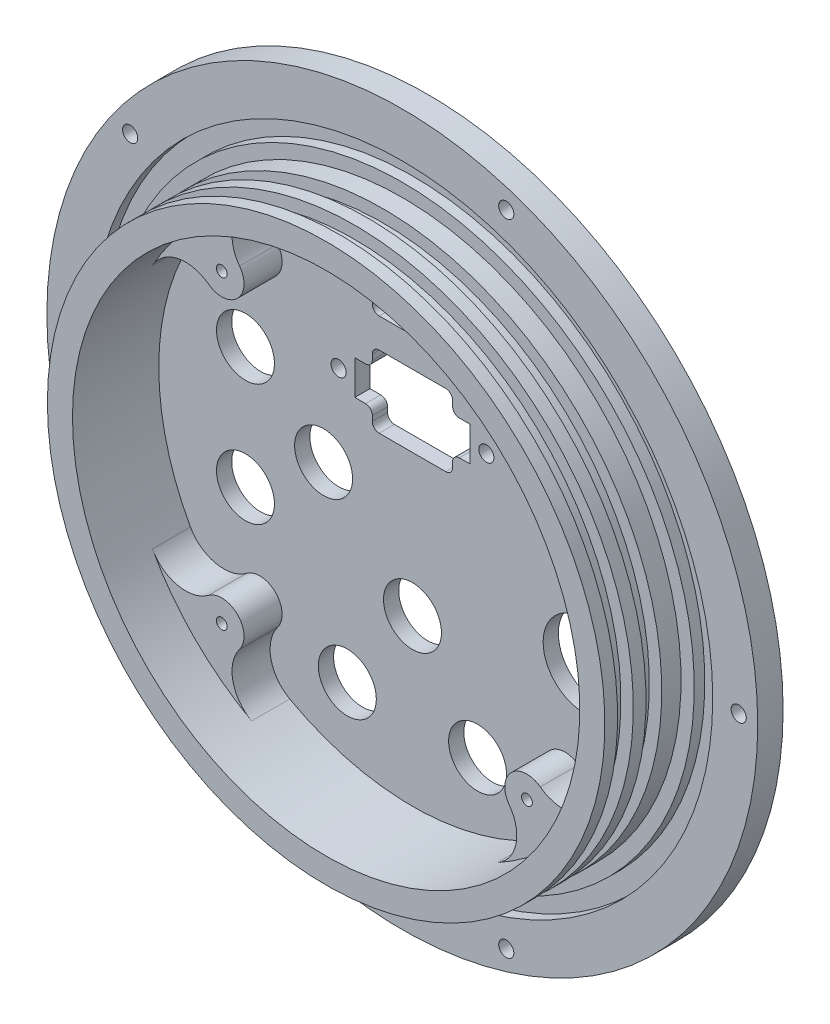
SolidWorks part; units mm, degrees
material "6061-T6 (SS)"
ref_plane "Front Plane" through (0, 0, 0) normal (0, 0, 1) x (1, 0, 0)
ref_plane "Top Plane" through (0, 0, 0) normal (0, 1, 0) x (1, 0, 0)
ref_plane "Right Plane" through (0, 0, 0) normal (1, 0, 0) x (0, 0, -1)
sketch "Sketch1" plane through (0, 0, 0) normal (0, 1, 0) x (1, 0, 0)
  line L0 (0, 0) -> (0, -25.4) construction
  line L1 (0, 0) -> (88.9, 0)
  line L2 (63.4492, -25.4) -> (69.723, -25.4)
  line L3 (69.723, -25.4) -> (69.723, -22.225)
  line L4 (63.4492, -25.4) -> (63.4492, -3.81)
  line L5 (63.4492, -3.81) -> (0, -3.81)
  line L6 (0, -3.81) -> (0, 0)
  line L7 (88.9, 0) -> (88.9, -6.35)
  line L8 (73.025, -3.7084) -> (77.6478, -3.7084)
  line L9 (73.025, -3.7084) -> (73.025, -6.35)
  line L10 (73.025, -6.35) -> (69.723, -6.35)
  line L11 (77.6478, -3.7084) -> (77.6478, -6.35)
  line L12 (77.6478, -6.35) -> (88.9, -6.35)
  line L13 (69.723, -22.225) -> (66.6242, -22.225)
  line L14 (66.6242, -22.225) -> (66.6242, -18.288)
  line L15 (66.6242, -18.288) -> (69.723, -18.288)
  line L16 (69.723, -15.113) -> (66.6242, -15.113)
  line L17 (66.6242, -15.113) -> (66.6242, -11.176)
  line L18 (66.6242, -11.176) -> (69.723, -11.176)
  line L19 (69.723, -11.176) -> (69.723, -6.35)
  line L20 (69.723, -18.288) -> (69.723, -15.113)
  dimension "D1" = 139.446
  dimension "D2" = 6.35
  dimension "D3" = 177.8
  dimension "D4" = 146.05
  dimension "D5" = 3.175
  dimension "D6" = 19.05
  dimension "D7" = 4.6228
  dimension "D8" = 2.6416
  dimension "D9" = 3.0988
  dimension "D10" = 3.937
  dimension "D11" = 3.175
  dimension "D12" = 3.175
  dimension "D13" = 3.81
revolve "Revolve1" add sketch "Sketch1" angle 360 about L0
hole_wizard "#6 Clearance Hole1" positions "Sketch3" profile "Sketch2" hole size "#6" standard "ANSI Inch"
sketch "Sketch3" plane through (0, 0, 6.35) normal (0, 0, 1) x (1, 0, 0)
  line L14 (0, 77.6478) -> (0, 83.2739) construction
  line L17 (0, 83.2739) -> (0, 88.9) construction
  line L19 (0, 0) -> (84.1375, 0) construction
  circle A6 centre (0, 0) radius 84.1375
  circle A7 centre (0, 0) radius 77.6478 construction
  circle A8 centre (0, 0) radius 88.9 construction
  point P192 (84.1375, 0)
  point P208 (25.9999, -80.0195)
  point P209 (-68.0687, -49.4548)
  point P210 (-68.0687, 49.4548)
  point P211 (25.9999, 80.0195)
  dimension "D1" = 5
  dimension "D2" = 168.275
sketch "Sketch2" plane through (84.1375, 0, 6.35) normal (1, 0, 0) x (0, -1, 0)
  line L0 (0, 0) -> (0, 26.5408)
  line L1 (0, 26.5408) -> (1.8986, 25.4)
  line L2 (1.8986, 25.4) -> (1.8986, 0)
  line L5 (1.8986, 0) -> (0, 0)
  line L10 (0, 26.5408) -> (-1.8986, 25.4) construction
  line L11 (0, -6.35) -> (0, 107.95) construction
  dimension "Hole Dia." = 3.7973
  dimension "Hole Depth" = 25.4
  dimension "Drill Angle" = 118
sketch "Sketch4" plane through (0, 0, 3.81) normal (0, 0, 1) x (1, 0, 0)
  line L0 (0, 0) -> (0, 122.2661) construction
  line L1 (-11.7348, 51.9303) -> (-14.4272, 51.9303)
  line L2 (8.3312, 38.6207) -> (-8.3312, 38.6207)
  line L3 (10.033, 40.3225) -> (10.033, 41.6179)
  line L4 (8.3312, 56.6293) -> (-8.3312, 56.6293)
  line L5 (-10.033, 40.3225) -> (-10.033, 41.6179)
  line L6 (10.033, 38.6207) -> (-10.033, 56.6293) construction
  line L7 (10.033, 56.6293) -> (-10.033, 38.6207) construction
  line L8 (-14.4272, 51.9303) -> (-14.4272, 43.3197)
  line L9 (-14.4272, 43.3197) -> (-11.7348, 43.3197)
  line L10 (14.4272, 43.3197) -> (11.7348, 43.3197)
  line L11 (14.4272, 51.9303) -> (14.4272, 43.3197)
  line L12 (11.7348, 51.9303) -> (14.4272, 51.9303)
  line L13 (-14.4272, 47.625) -> (14.4272, 47.625) construction
  line L14 (-10.033, 53.6321) -> (-10.033, 54.9275)
  line L15 (10.033, 53.6321) -> (10.033, 54.9275)
  line L16 (-11.7348, 26.5303) -> (-14.4272, 26.5303)
  line L17 (8.3312, 13.2207) -> (-8.3312, 13.2207)
  line L18 (10.033, 14.9225) -> (10.033, 16.2179)
  line L19 (8.3312, 31.2293) -> (-8.3312, 31.2293)
  line L20 (-10.033, 14.9225) -> (-10.033, 16.2179)
  line L21 (10.033, 13.2207) -> (-10.033, 31.2293) construction
  line L22 (10.033, 31.2293) -> (-10.033, 13.2207) construction
  line L23 (-14.4272, 26.5303) -> (-14.4272, 17.9197)
  line L24 (-14.4272, 17.9197) -> (-11.7348, 17.9197)
  line L25 (14.4272, 26.5303) -> (14.4272, 17.9197)
  line L26 (11.7348, 26.5303) -> (14.4272, 26.5303)
  line L27 (14.4272, 17.9197) -> (11.7348, 17.9197)
  line L28 (-14.4272, 22.225) -> (14.4272, 22.225) construction
  line L29 (-10.033, 28.2321) -> (-10.033, 29.5275)
  line L30 (10.033, 28.2321) -> (10.033, 29.5275)
  line L31 (0, 0) -> (37.8444, 0) construction
  line L32 (-14.4272, -22.225) -> (14.4272, -22.225)
  line L33 (10.033, -31.2293) -> (-10.033, -13.2207)
  line L34 (10.033, -13.2207) -> (-10.033, -31.2293)
  line L35 (-14.4272, -47.625) -> (14.4272, -47.625)
  line L36 (10.033, -56.6293) -> (-10.033, -38.6207)
  line L37 (10.033, -38.6207) -> (-10.033, -56.6293)
  line L38 (10.033, -28.2321) -> (10.033, -29.5275) construction
  line L39 (-10.033, -28.2321) -> (-10.033, -29.5275) construction
  line L40 (14.4272, -17.9197) -> (11.7348, -17.9197) construction
  line L41 (11.7348, -26.5303) -> (14.4272, -26.5303) construction
  line L42 (14.4272, -26.5303) -> (14.4272, -17.9197) construction
  line L43 (-14.4272, -17.9197) -> (-11.7348, -17.9197) construction
  line L44 (-14.4272, -26.5303) -> (-14.4272, -17.9197) construction
  line L45 (-10.033, -14.9225) -> (-10.033, -16.2179) construction
  line L46 (8.3312, -31.2293) -> (-8.3312, -31.2293) construction
  line L47 (10.033, -14.9225) -> (10.033, -16.2179) construction
  line L48 (8.3312, -13.2207) -> (-8.3312, -13.2207) construction
  line L49 (-11.7348, -26.5303) -> (-14.4272, -26.5303) construction
  line L50 (10.033, -53.6321) -> (10.033, -54.9275) construction
  line L51 (-10.033, -53.6321) -> (-10.033, -54.9275) construction
  line L52 (11.7348, -51.9303) -> (14.4272, -51.9303) construction
  line L53 (14.4272, -51.9303) -> (14.4272, -43.3197) construction
  line L54 (14.4272, -43.3197) -> (11.7348, -43.3197) construction
  line L55 (-14.4272, -43.3197) -> (-11.7348, -43.3197) construction
  line L56 (-14.4272, -51.9303) -> (-14.4272, -43.3197) construction
  line L57 (-10.033, -40.3225) -> (-10.033, -41.6179) construction
  line L58 (8.3312, -56.6293) -> (-8.3312, -56.6293) construction
  line L59 (10.033, -40.3225) -> (10.033, -41.6179) construction
  line L60 (8.3312, -38.6207) -> (-8.3312, -38.6207) construction
  line L61 (-11.7348, -51.9303) -> (-14.4272, -51.9303) construction
  line L62 (-14.4272, 22.225) -> (14.4272, 22.225) construction
  arc A0 (-11.7348, 43.3197) -> (-10.033, 41.6179) centre (-11.7348, 41.6179) cw
  arc A1 (11.7348, 43.3197) -> (10.033, 41.6179) centre (11.7348, 41.6179) ccw
  arc A2 (11.7348, 51.9303) -> (10.033, 53.6321) centre (11.7348, 53.6321) cw
  arc A3 (-11.7348, 51.9303) -> (-10.033, 53.6321) centre (-11.7348, 53.6321) ccw
  arc A4 (-8.3312, 38.6207) -> (-10.033, 40.3225) centre (-8.3312, 40.3225) cw
  arc A5 (8.3312, 38.6207) -> (10.033, 40.3225) centre (8.3312, 40.3225) ccw
  arc A6 (10.033, 54.9275) -> (8.3312, 56.6293) centre (8.3312, 54.9275) ccw
  arc A7 (-8.3312, 56.6293) -> (-10.033, 54.9275) centre (-8.3312, 54.9275) ccw
  arc A8 (-11.7348, 17.9197) -> (-10.033, 16.2179) centre (-11.7348, 16.2179) cw
  arc A9 (-8.3312, 13.2207) -> (-10.033, 14.9225) centre (-8.3312, 14.9225) cw
  arc A10 (8.3312, 13.2207) -> (10.033, 14.9225) centre (8.3312, 14.9225) ccw
  arc A11 (11.7348, 17.9197) -> (10.033, 16.2179) centre (11.7348, 16.2179) ccw
  arc A12 (11.7348, 26.5303) -> (10.033, 28.2321) centre (11.7348, 28.2321) cw
  arc A13 (10.033, 29.5275) -> (8.3312, 31.2293) centre (8.3312, 29.5275) ccw
  arc A14 (-8.3312, 31.2293) -> (-10.033, 29.5275) centre (-8.3312, 29.5275) ccw
  arc A15 (-11.7348, 26.5303) -> (-10.033, 28.2321) centre (-11.7348, 28.2321) ccw
  arc A16 (-11.7348, -26.5303) -> (-10.033, -28.2321) centre (-11.7348, -28.2321) cw construction
  arc A17 (-8.3312, -31.2293) -> (-10.033, -29.5275) centre (-8.3312, -29.5275) cw construction
  arc A18 (10.033, -29.5275) -> (8.3312, -31.2293) centre (8.3312, -29.5275) cw construction
  arc A19 (11.7348, -26.5303) -> (10.033, -28.2321) centre (11.7348, -28.2321) ccw construction
  arc A20 (11.7348, -17.9197) -> (10.033, -16.2179) centre (11.7348, -16.2179) cw construction
  arc A21 (8.3312, -13.2207) -> (10.033, -14.9225) centre (8.3312, -14.9225) cw construction
  arc A22 (-8.3312, -13.2207) -> (-10.033, -14.9225) centre (-8.3312, -14.9225) ccw construction
  arc A23 (-11.7348, -17.9197) -> (-10.033, -16.2179) centre (-11.7348, -16.2179) ccw construction
  arc A24 (-8.3312, -56.6293) -> (-10.033, -54.9275) centre (-8.3312, -54.9275) cw construction
  arc A25 (10.033, -54.9275) -> (8.3312, -56.6293) centre (8.3312, -54.9275) cw construction
  arc A26 (8.3312, -38.6207) -> (10.033, -40.3225) centre (8.3312, -40.3225) cw construction
  arc A27 (-8.3312, -38.6207) -> (-10.033, -40.3225) centre (-8.3312, -40.3225) ccw construction
  arc A28 (-11.7348, -51.9303) -> (-10.033, -53.6321) centre (-11.7348, -53.6321) cw construction
  arc A29 (11.7348, -51.9303) -> (10.033, -53.6321) centre (11.7348, -53.6321) ccw construction
  arc A30 (11.7348, -43.3197) -> (10.033, -41.6179) centre (11.7348, -41.6179) cw construction
  arc A31 (-11.7348, -43.3197) -> (-10.033, -41.6179) centre (-11.7348, -41.6179) ccw construction
  point P4 (0, 47.625)
  point P21 (-10.033, 43.3197)
  point P24 (10.033, 43.3197)
  point P27 (10.033, 51.9303)
  point P30 (-10.033, 51.9303)
  point P43 (0, 22.225)
  point P60 (-10.033, 17.9197)
  point P69 (10.033, 17.9197)
  point P72 (10.033, 26.5303)
  point P81 (-10.033, 26.5303)
  point P151 (-10.033, -26.5303)
  point P152 (10.033, -26.5303)
  point P153 (10.033, -17.9197)
  point P154 (-10.033, -17.9197)
  point P155 (0, -22.225)
  point P156 (-10.033, -51.9303)
  point P157 (10.033, -51.9303)
  point P158 (10.033, -43.3197)
  point P159 (-10.033, -43.3197)
  point P160 (0, -47.625)
  dimension "D6" = 1.7018
  dimension "D7" = 1.7018
  dimension "D8" = 1.7018
  dimension "D9" = 1.7018
  dimension "D10" = 1.7018
  dimension "D11" = 1.7018
  dimension "D12" = 1.7018
  dimension "D13" = 1.7018
  dimension "D14" = 1.7018
  dimension "D15" = 1.7018
  dimension "D16" = 1.7018
  dimension "D17" = 1.7018
  dimension "D18" = 1.7018
  dimension "D19" = 1.7018
  dimension "D20" = 1.7018
  dimension "D21" = 1.7018
  dimension "D1" = 20.066
  dimension "D2" = 28.8544
  dimension "D3" = 8.6106
  dimension "D4" = 18.0086
  dimension "D5" = 47.625
  dimension "D22" = 22.225
extrude "Cut-Extrude1" cut sketch "Sketch4" against normal through all contours A15 L16 L23 L24 A8 L20 A9 L17 A10 L18 A11 L27 L25 L26 A12 L30 A13 L19 A14 L29 | L4 A7 L14 A3 L1 L8 L9 A0 L5 A4 L2 A5 L3 A1 L10 L11 L12 A2 L15 A6 region at (0, 47.625, 3.81) region at (0, 22.225, 3.81)
hole_wizard "#6 Clearance Hole2" positions "Sketch6" profile "Sketch5" hole size "#6" standard "ANSI Inch"
sketch "Sketch6" plane through (0, 0, 3.81) normal (0, 0, 1) x (1, 0, 0)
  line L0 (0, 38.6207) -> (0, 56.6293) construction
  line L1 (-8.3312, 38.6207) -> (8.3312, 38.6207) construction
  line L2 (8.3312, 56.6293) -> (-8.3312, 56.6293) construction
  line L5 (-14.4272, 47.625) -> (14.4272, 47.625) construction
  line L6 (-14.4272, 51.9303) -> (-14.4272, 43.3197) construction
  line L7 (14.4272, 43.3197) -> (14.4272, 51.9303) construction
  line L8 (-14.4272, 22.225) -> (14.4272, 22.225) construction
  line L9 (-14.4272, 26.5303) -> (-14.4272, 17.9197) construction
  line L10 (14.4272, 17.9197) -> (14.4272, 26.5303) construction
  point P21 (-18.4785, 47.625)
  point P24 (18.4785, 47.625)
  point P35 (-18.4785, 22.225)
  point P37 (18.4785, 22.225)
  dimension "D1" = 36.957
sketch "Sketch5" plane through (-18.4785, 47.625, 3.81) normal (1, 0, 0) x (0, -1, 0)
  line L0 (0, 0) -> (0, 9.0148)
  line L1 (0, 9.0148) -> (1.8986, 7.874)
  line L2 (1.8986, 7.874) -> (1.8986, 0)
  line L5 (1.8986, 0) -> (0, 0)
  line L10 (0, 9.0148) -> (-1.8987, 7.874) construction
  line L11 (0, -6.35) -> (0, 107.95) construction
  dimension "Hole Dia." = 3.7973
  dimension "Hole Depth" = 7.874
  dimension "Drill Angle" = 118
sketch "Sketch11" plane through (0, 0, 3.81) normal (0, 0, 1) x (1, 0, 0)
  line L0 (-38.1661, 38.1661) -> (38.1661, 38.1661) construction
  line L1 (38.1661, 38.1661) -> (38.1661, -38.1661) construction
  line L2 (38.1661, -38.1661) -> (-38.1661, -38.1661) construction
  line L3 (-38.1661, -38.1661) -> (-38.1661, 38.1661) construction
  line L4 (-41.8875, 34.0402) -> (-48.9307, 40.393)
  line L5 (-34.0402, 41.8875) -> (-40.393, 48.9307)
  line L6 (0, 0) -> (0, 31.159) construction
  line L7 (0, 0) -> (24.8539, 0) construction
  line L8 (41.8875, 34.0402) -> (48.9307, 40.393)
  line L9 (34.0402, 41.8875) -> (40.393, 48.9307)
  line L10 (41.8875, -34.0402) -> (48.9307, -40.393)
  line L11 (34.0402, -41.8875) -> (40.393, -48.9307)
  line L12 (-41.8875, -34.0402) -> (-48.9307, -40.393)
  line L13 (-34.0402, -41.8875) -> (-40.393, -48.9307)
  line L14 (-38.1661, 38.1661) -> (0, 0) construction
  circle A0 centre (0, 0) radius 53.975 construction
  circle A1 centre (-38.1661, 38.1661) radius 5.5562
  circle A2 centre (38.1661, 38.1661) radius 5.5562
  circle A3 centre (38.1661, -38.1661) radius 5.5562
  circle A4 centre (-38.1661, -38.1661) radius 5.5562
  circle A5 centre (0, 0) radius 63.4492 construction
  circle A6 centre (0, 0) radius 63.4492 construction
  arc A7 (-40.393, 48.9307) -> (-48.9307, 40.393) centre (0, 0) ccw
  arc A8 (-48.9307, -40.393) -> (-40.393, -48.9307) centre (0, 0) ccw
  arc A9 (40.393, -48.9307) -> (48.9307, -40.393) centre (0, 0) ccw
  arc A10 (48.9307, 40.393) -> (40.393, 48.9307) centre (0, 0) ccw
  dimension "D1" = 107.95
  dimension "D2" = 11.1125
extrude "Boss-Extrude1" add sketch "Sketch11" along normal blind 9.525 contours L5 A7 L4 A1 | A1 | A2 | L8 A10 L9 A2 | A3 | L11 A9 L10 A3 | L12 A8 L13 A4 | A4 region at (-42.8886, 42.8886, 3.81) region at (-38.1661, 38.1661, 3.81) region at (42.8886, 42.8886, 3.81) region at (38.1661, 38.1661, 3.81) region at (42.8886, -42.8886, 3.81) region at (38.1661, -38.1661, 3.81) region at (-42.8886, -42.8886, 3.81) region at (-38.1661, -38.1661, 3.81)
sketch "Sketch7" plane through (0, 0, 3.81) normal (0, 0, 1) x (1, 0, 0)
  line L0 (52.7617, -8.5918) -> (49.9889, -18.9401)
  line L1 (0, 0) -> (44.45, 0) construction
  line L3 (0, 0) -> (-44.45, 0) construction
  line L4 (0, 0) -> (51.3753, -13.766) construction
  arc A0 (52.7617, -8.5918) -> (49.9889, -18.9401) centre (42.9354, -11.5045) ccw
  circle A2 centre (0, 0) radius 44.45 construction
  dimension "D1" = 20.4978
  dimension "D3" = 88.9
  dimension "D2" = 8.7376
  dimension "D4" = 15
extrude "Cut-Extrude2" cut sketch "Sketch7" against normal through all
fillet "Fillet1" radius 9.525 8 edges at (-48.9307, -40.393, 8.5725) (-40.393, -48.9307, 8.5725) (40.393, -48.9307, 8.5725) (48.9307, -40.393, 8.5725) (48.9307, 40.393, 8.5725) (40.393, 48.9307, 8.5725) (-40.393, 48.9307, 8.5725) (-48.9307, 40.393, 8.5725)
hole_wizard "M16x1.5 Tapped Hole1" positions "Sketch9" profile "Sketch8" tap size "M16x1.5" standard "ANSI Metric"
sketch "Sketch9" plane through (0, 0, 3.81) normal (0, 0, 1) x (1, 0, 0)
  line L7 (0, 0) -> (42.9354, -11.5045) construction
  line L11 (-41.7693, 15.2028) -> (0, 0) construction
  line L13 (0, 0) -> (-59.9493, 0) construction
  line L14 (0, 0) -> (0, -60.9622) construction
  line L15 (0, 0) -> (18.9657, -52.108) construction
  line L16 (0, 0) -> (50.7536, 18.4728) construction
  circle A3 centre (0, 0) radius 44.45
  circle A5 centre (0, 0) radius 47.625
  circle A6 centre (0, 0) radius 22.225
  point P14 (44.7529, 16.2887)
  point P59 (-22.225, 0)
  point P98 (0, -22.225)
  point P112 (-16.2887, -44.7529)
  point P114 (-41.7693, 15.2028)
  point P116 (-41.7693, -15.2028)
  point P118 (16.2887, -44.7529)
  dimension "D1" = 20
  dimension "D3" = 20
  dimension "D7" = 95.25
  dimension "D2" = 44.45
  dimension "D6" = 20
sketch "Sketch8" plane through (44.7529, 16.2887, 3.81) normal (1, 0, 0) x (0, -1, 0)
  line L0 (0, 0) -> (0, 40.9322)
  line L1 (0, 40.9322) -> (7.25, 36.576)
  line L2 (7.25, 36.576) -> (7.25, 0)
  line L5 (7.25, 0) -> (0, 0)
  line L10 (0, 40.9322) -> (-7.25, 36.576) construction
  line L11 (0, -6.35) -> (0, 107.95) construction
  dimension "Tap Drill Dia." = 14.5
  dimension "Tap Drill Depth" = 36.576
  dimension "Drill Angle" = 118
sketch "Sketch10" [suppressed] plane through (0, 0, 3.8118) normal (0, 0, 1) x (1, 0, 0)
  line L0 (-35.921, -35.921) -> (35.921, 35.921) construction
  line L1 (35.921, -35.921) -> (-35.921, 35.921) construction
  line L2 (0, 0) -> (48.0872, 0) construction
  circle A0 centre (0, 0) radius 50.8
  dimension "D1" = 101.6
  dimension "D2" = 90
  dimension "D3" = 45
hole_wizard "#6-32 Tapped Hole2" positions "Sketch14" profile "Sketch13" tap size "#6-32" standard "ANSI Inch"
sketch "Sketch14" plane through (0, 0, 13.335) normal (0, 0, 1) x (1, 0, 0)
  point P0 (-38.1661, 38.1661)
  point P3 (38.1661, 38.1661)
  point P6 (38.1661, -38.1661)
  point P9 (-38.1661, -38.1661)
sketch "Sketch13" plane through (-38.1661, 38.1661, 13.335) normal (1, 0, 0) x (0, -1, 0)
  line L0 (0, 0) -> (0, 10.2107)
  line L1 (0, 10.2107) -> (1.3525, 9.398)
  line L2 (1.3525, 9.398) -> (1.3525, 0)
  line L5 (1.3525, 0) -> (0, 0)
  line L10 (0, 10.2107) -> (-1.3525, 9.398) construction
  line L11 (0, -6.35) -> (0, 107.95) construction
  dimension "Tap Drill Dia." = 2.7051
  dimension "Tap Drill Depth" = 9.398
  dimension "Drill Angle" = 118
